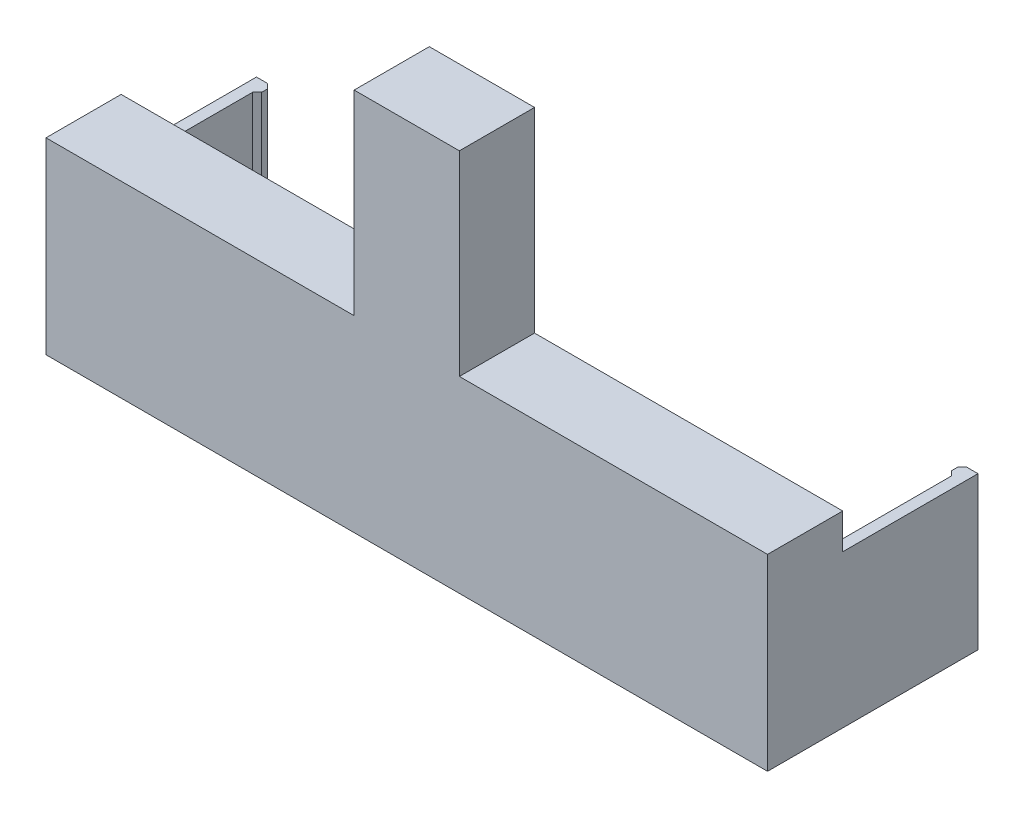
SolidWorks part; units mm, degrees
ref_plane "Front Plane" through (0, 0, 0) normal (0, 0, 1) x (1, 0, 0)
ref_plane "Top Plane" through (0, 0, 0) normal (0, 1, 0) x (1, 0, 0)
ref_plane "Right Plane" through (0, 0, 0) normal (1, 0, 0) x (0, 0, -1)
sketch "Display Rough Dim" plane through (0, 0, 0) normal (0, 0, 1) x (1, 0, 0)
  line L1 (-46.5, 48.5) -> (46.5, 48.5)
  line L2 (-46.5, 48.5) -> (-46.5, -48.5)
  line L3 (-46.5, -48.5) -> (46.5, -48.5)
  line L4 (46.5, 48.5) -> (46.5, -48.5)
  line L5 (-46.5, 48.5) -> (46.5, -48.5) construction
  line L6 (-46.5, -48.5) -> (46.5, 48.5) construction
  point P0 (0, 0)
  dimension "D1" = 93
  dimension "D2" = 97
sketch "Sketch1" plane through (0, 0, 0) normal (0, 0, 1) x (1, 0, 0)
  line L0 (-46.5, 48.5) -> (46.5, 48.5) construction
  line L1 (-48, 12.5) -> (48, 12.5)
  line L2 (-48, 12.5) -> (-48, -12.5)
  line L3 (-48, -12.5) -> (48, -12.5)
  line L4 (48, 12.5) -> (48, -12.5)
  line L5 (-48, 12.5) -> (48, -12.5) construction
  line L6 (-48, -12.5) -> (48, 12.5) construction
  line L7 (-7, 12.5) -> (-7, 38.5)
  line L8 (-7, 38.5) -> (7, 38.5)
  line L9 (7, 38.5) -> (7, 12.5)
  line L10 (46.5, 12.5) -> (46.5, -12.5)
  line L11 (46.5, 48.5) -> (46.5, -48.5) construction
  line L12 (-46.5, 12.5) -> (-46.5, -12.5)
  line L13 (-46.5, 48.5) -> (-46.5, -48.5) construction
  circle A0 centre (0, 31.5) radius 2
  point P0 (0, 0)
  point P14 (0, 38.5)
  dimension "D3" = 17
  dimension "D4" = 4
  dimension "D6" = 7
  dimension "D1" = 96
  dimension "D2" = 25
  dimension "D5" = 7
extrude "Boss-Extrude1" add sketch "Sketch1" along normal blind 10 contours L1 L12 L3 L10 | L12 L1 L2 L3 | L1 L10 L3 L4 | L9 L8 L7 L1 A0 | A0 region at (-47.25, 0, 0) region at (0, 0, 0) region at (0, 25.2855, 0) region at (47.25, 0, 0) region at (0, 31.5, 0)
extrude "Boss-Extrude2" add sketch "Sketch1<3>" against normal blind 18 contours L1 L10 L3 L4 | L12 L1 L2 L3 region at (-47.25, 0, 0) region at (47.25, 0, 0)
sketch "Sketch1<3>" plane through (0, 0, 0) normal (0, 0, 1) x (1, 0, 0) same geometry as "Sketch1"
extrude "Boss-Extrude3" add sketch "Sketch1<4>" against normal blind 5 contours A0
sketch "Sketch1<4>" plane through (0, 0, 0) normal (0, 0, 1) x (1, 0, 0) same geometry as "Sketch1"
sketch "Sketch5" plane through (0, 12.5, 0) normal (0, 1, 0) x (1, 0, 0)
  line L0 (-46.5, 18) -> (-45.5, 17)
  line L1 (-45.5, 17) -> (-46.5, 16)
  line L2 (-46.5, 18) -> (-46.5, 0) construction
  line L3 (-46.5, 16) -> (-43, 16) construction
  line L4 (-43, 16) -> (-43, 18) construction
  line L5 (-43, 18) -> (-46.5, 16) construction
  line L6 (-45.9, 17.4) -> (-45.9, 16.6)
  line L7 (0, 0) -> (0, 13.3207) construction
  line L8 (-48, 0) -> (48, 0) construction
  line L9 (45.5, 17) -> (46.5, 16)
  line L10 (46.5, 18) -> (45.5, 17)
  line L11 (45.9, 17.4) -> (45.9, 16.6)
  line L12 (46.5, 16) -> (46.5, 18)
  line M7 (-46.5, 0) -> (-46.5, 18)
  dimension "D1" = 3.5
  dimension "D2" = 2
  dimension "D3" = 135
  dimension "D4" = 0.6
extrude "Boss-Extrude4" add sketch "Sketch5" along direction (0, -1, 0) on the side against the normal up to surface (25 mm away) contours L9 L12 L10 L11 | L6 L0 L1 M7 region at (-46.2429, 12.5, -17) region at (46.2429, 12.5, -17) up to face at (0, -12.5, -6.5)
sketch "Sketch7" plane through (0, 12.5, 0) normal (0, 1, 0) x (1, 0, 0)
  line L0 (46.5, 0) -> (48, 0)
  line L1 (-48, 0) -> (48, 0) construction
  line L3 (-46.5, 0) -> (-48, 0)
  line L4 (-48, 0) -> (48, 0) construction
  line L12 (46.5, 0) -> (7, 0)
  line L13 (7, 0) -> (7, -10)
  line L14 (7, -10) -> (48, -10)
  line L15 (48, -10) -> (48, 18)
  line L16 (48, 18) -> (46.5, 18)
  line L17 (46.5, 18) -> (45.9, 17.4)
  line L18 (45.9, 17.4) -> (45.9, 16.6)
  line L19 (45.9, 16.6) -> (46.5, 16)
  line L20 (46.5, 16) -> (46.5, 0)
  line L21 (46.5, 0) -> (7, 0)
  line L22 (7, 0) -> (7, -10)
  line L23 (7, -10) -> (48, -10)
  line L24 (48, -10) -> (48, 18)
  line L25 (48, 18) -> (46.5, 18)
  line L26 (46.5, 18) -> (45.9, 17.4)
  line L27 (45.9, 17.4) -> (45.9, 16.6)
  line L28 (45.9, 16.6) -> (46.5, 16)
  line L29 (46.5, 16) -> (46.5, 0)
  line L30 (-7, 0) -> (-46.5, 0)
  line L31 (-46.5, 0) -> (-46.5, 16)
  line L32 (-46.5, 16) -> (-45.9, 16.6)
  line L33 (-45.9, 16.6) -> (-45.9, 17.4)
  line L34 (-45.9, 17.4) -> (-46.5, 18)
  line L35 (-46.5, 18) -> (-48, 18)
  line L36 (-48, 18) -> (-48, -10)
  line L37 (-48, -10) -> (-7, -10)
  line L38 (-7, -10) -> (-7, 0)
  line L39 (-7, 0) -> (-46.5, 0)
  line L40 (-46.5, 0) -> (-46.5, 16)
  line L41 (-46.5, 16) -> (-45.9, 16.6)
  line L42 (-45.9, 16.6) -> (-45.9, 17.4)
  line L43 (-45.9, 17.4) -> (-46.5, 18)
  line L44 (-46.5, 18) -> (-48, 18)
  line L45 (-48, 18) -> (-48, -10)
  line L46 (-48, -10) -> (-7, -10)
  line L47 (-7, -10) -> (-7, 0)
  line M22 (48, -10) -> (48, 18)
  line M23 (48, 18) -> (46.5, 18)
  line M24 (46.5, 18) -> (45.9, 17.4)
  line M25 (45.9, 17.4) -> (45.9, 16.6)
  line M26 (45.9, 16.6) -> (46.5, 16)
  line M27 (46.5, 16) -> (46.5, 0)
  dimension "D1" = 0
  dimension "D2" = 0
extrude "Cut-Extrude1" cut sketch "Sketch7" against normal blind 4.7 contours L0 M27 M22 M23 M24 M25 M26 region at (47.2196, 12.5, -9.2414)
extrude "Cut-Extrude2" cut sketch "Sketch7<4>" against normal blind 7 contours L44 L45 L3 L40 L41 L42 L43 region at (-47.2196, 12.5, -9.2414)
sketch "Sketch7<4>" plane through (0, 12.5, 0) normal (0, 1, 0) x (1, 0, 0) same geometry as "Sketch7"
equation "\"DisplayHeight\"= 18mm"
equation "\"DisplayWidth\"= 93mm"
equation "\"DisplayTall\"= 97mm"
